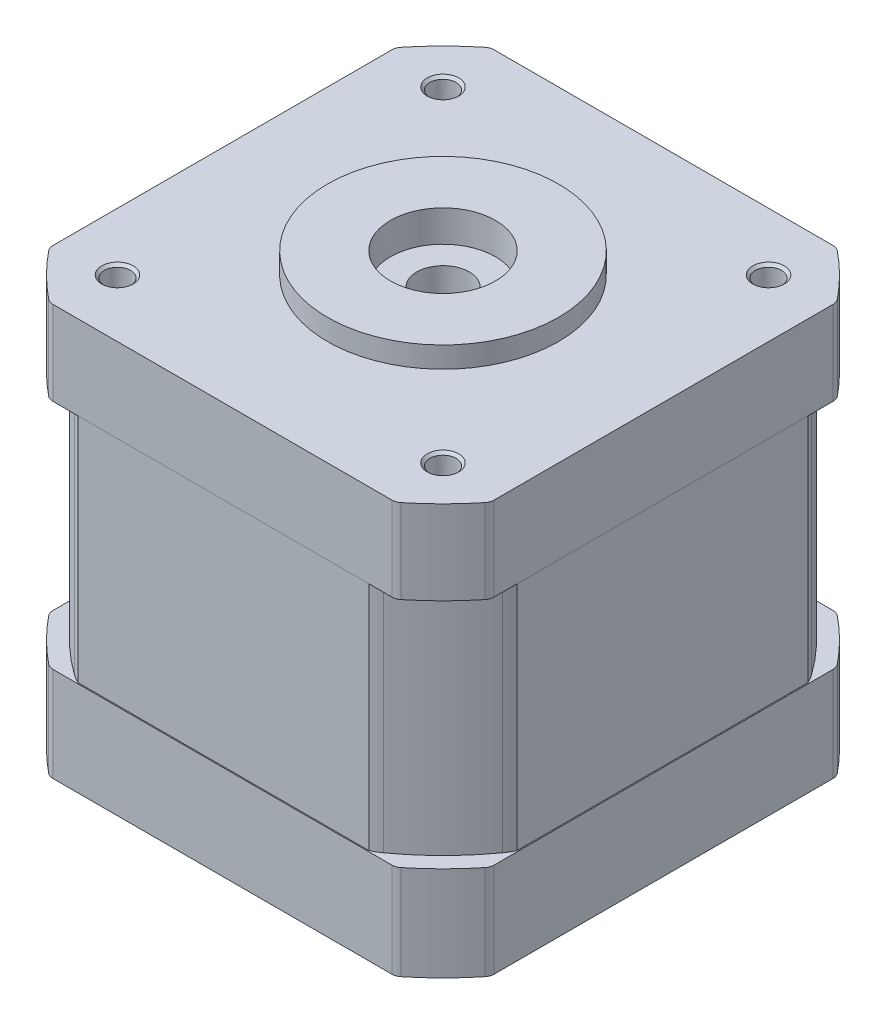
SolidWorks part; units mm, degrees
ref_plane "Front Plane" through (0, 0, 0) normal (0, 0, 1) x (1, 0, 0)
ref_plane "Top Plane" through (0, 0, 0) normal (0, 1, 0) x (1, 0, 0)
ref_plane "Right Plane" through (0, 0, 0) normal (1, 0, 0) x (0, 0, -1)
sketch "Sketch1" plane through (0, 0, 0) normal (0, 0, 1) x (1, 0, 0)
  line L0 (5, 0) -> (11, 0)
  line L1 (11, 0) -> (11, -2)
  line L2 (11, -2) -> (26.7, -2)
  line L3 (26.7, -2) -> (26.7, -10)
  line L4 (26.7, -41.1) -> (5, -41.1)
  line L5 (2.5, -38.1) -> (2.5, -32.1)
  line L6 (2.5, -32.1) -> (11, -32.1)
  line L7 (11, -32.1) -> (11, -10)
  line L8 (11, -10) -> (2.5, -10)
  line L9 (2.5, -10) -> (2.5, -3)
  line L10 (0, 0) -> (0, -41.1) construction
  line L11 (26.7, -10) -> (25.15, -10)
  line L12 (25.15, -10) -> (25.15, -32.1)
  line L13 (25.15, -32.1) -> (26.7, -32.1)
  line L14 (26.7, -32.1) -> (26.7, -41.1)
  line L15 (2.5, -38.1) -> (5, -38.1)
  line L16 (5, -38.1) -> (5, -41.1)
  line L17 (5, 0) -> (5, -3)
  line L18 (5, -3) -> (2.5, -3)
  dimension "D1" = 8
  dimension "D2" = 9
  dimension "D3" = 26.7
  dimension "D4" = 25.15
  dimension "D5" = 11
  dimension "D6" = 5
  dimension "D7" = 3
  dimension "D8" = 5
  dimension "D9" = 2
  dimension "D10" = 39.1
revolve "Revolve1" add sketch "Sketch1" angle 360 about L10
sketch "Sketch2" plane through (0, -2, 0) normal (0, 1, 0) x (1, 0, 0)
  line L1 (-21, 21) -> (21, 21)
  line L2 (-21, 21) -> (-21, -21)
  line L3 (-21, -21) -> (21, -21)
  line L4 (21, 21) -> (21, -21)
  line L5 (-21, 21) -> (21, -21) construction
  line L6 (-21, -21) -> (21, 21) construction
  line L7 (-27.5, 27.5) -> (27.5, 27.5)
  line L8 (-27.5, 27.5) -> (-27.5, -27.5)
  line L9 (-27.5, -27.5) -> (27.5, -27.5)
  line L10 (27.5, 27.5) -> (27.5, -27.5)
  line L11 (-27.5, 27.5) -> (27.5, -27.5) construction
  line L12 (-27.5, -27.5) -> (27.5, 27.5) construction
  point P0 (0, 0)
  point P6 (0, 0)
  dimension "D1" = 42
  dimension "D2" = 55
extrude "Cut-Extrude1" cut sketch "Sketch2" against normal through all
sketch "Sketch3" plane through (0, -10, 0) normal (0, -1, 0) x (1, 0, 0)
  line L0 (-16.4891, 21) -> (16.4891, 21) construction
  line L1 (-21, 13.8392) -> (-20.9, 13.8392)
  line L2 (-21, 13.8392) -> (-21, -13.8392)
  line L3 (-21, -13.8392) -> (-20.9, -13.8392)
  line L4 (-20.9, 13.8392) -> (-20.9, -13.8392)
  line L5 (-13.8392, -21) -> (13.8392, -21)
  line L6 (-13.8392, -21) -> (-13.8392, -20.9)
  line L7 (-13.8392, -20.9) -> (13.8392, -20.9)
  line L8 (13.8392, -21) -> (13.8392, -20.9)
  line L9 (21, -13.8392) -> (20.9, -13.8392)
  line L10 (21, -13.8392) -> (21, 13.8392)
  line L11 (21, 13.8392) -> (20.9, 13.8392)
  line L12 (20.9, -13.8392) -> (20.9, 13.8392)
  line L13 (-13.8392, 21) -> (13.8392, 21)
  line L14 (-13.8392, 21) -> (-13.8392, 20.9)
  line L15 (-13.8392, 20.9) -> (13.8392, 20.9)
  line L16 (13.8392, 21) -> (13.8392, 20.9)
  arc A0 (21, 13.8392) -> (13.8392, 21) centre (0, 0) ccw construction
  arc A1 (-21, -13.8392) -> (-13.8392, -21) centre (0, 0) ccw construction
  dimension "D1" = 0.1
extrude "Cut-Extrude2" cut sketch "Sketch3" along normal up to surface (22.1 mm away) up to face at (-18.2069, -32.1, -18.2069)
fillet "Fillet9" radius 5 8 edges at (13.8392, -21.05, -21) (21, -21.05, -13.8392) (21, -21.05, 13.8392) (13.8392, -21.05, 21) (-13.8392, -21.05, 21) (-21, -21.05, 13.8392) (-21, -21.05, -13.8392) (-13.8392, -21.05, -21)
fillet "Fillet10" radius 1 16 edges at (-21, -6, 16.4891) (-21, -6, -16.4891) (-16.4891, -6, -21) (16.4891, -6, -21) (16.4891, -36.6, -21) (-16.4891, -36.6, -21) (-21, -36.6, -16.4891) (-21, -36.6, 16.4891) (16.4891, -6, 21) (-16.4891, -6, 21) (-16.4891, -36.6, 21) (16.4891, -36.6, 21) (21, -36.6, 16.4891) (21, -36.6, -16.4891) (21, -6, -16.4891) (21, -6, 16.4891)
sketch "Sketch4" plane through (0, -2, 0) normal (0, 1, 0) x (1, 0, 0)
  line L1 (-15.5, 15.5) -> (15.5, 15.5) construction
  line L2 (-15.5, 15.5) -> (-15.5, -15.5) construction
  line L3 (-15.5, -15.5) -> (15.5, -15.5) construction
  line L4 (15.5, 15.5) -> (15.5, -15.5) construction
  line L5 (-15.5, 15.5) -> (15.5, -15.5) construction
  line L6 (-15.5, -15.5) -> (15.5, 15.5) construction
  circle A0 centre (-15.5, 15.5) radius 1.25
  circle A1 centre (15.5, 15.5) radius 1.25
  circle A2 centre (15.5, -15.5) radius 1.25
  circle A3 centre (-15.5, -15.5) radius 1.25
  point P0 (0, 0)
  dimension "D2" = 2.5
  dimension "D1" = 31
extrude "Cut-Extrude3" cut sketch "Sketch4" against normal blind 6
chamfer "Chamfer1" distance 0.25 angle 45 4 edges at (14.25, -2, -15.5) (14.25, -2, 15.5) (-16.75, -2, 15.5) (-16.75, -2, -15.5)
